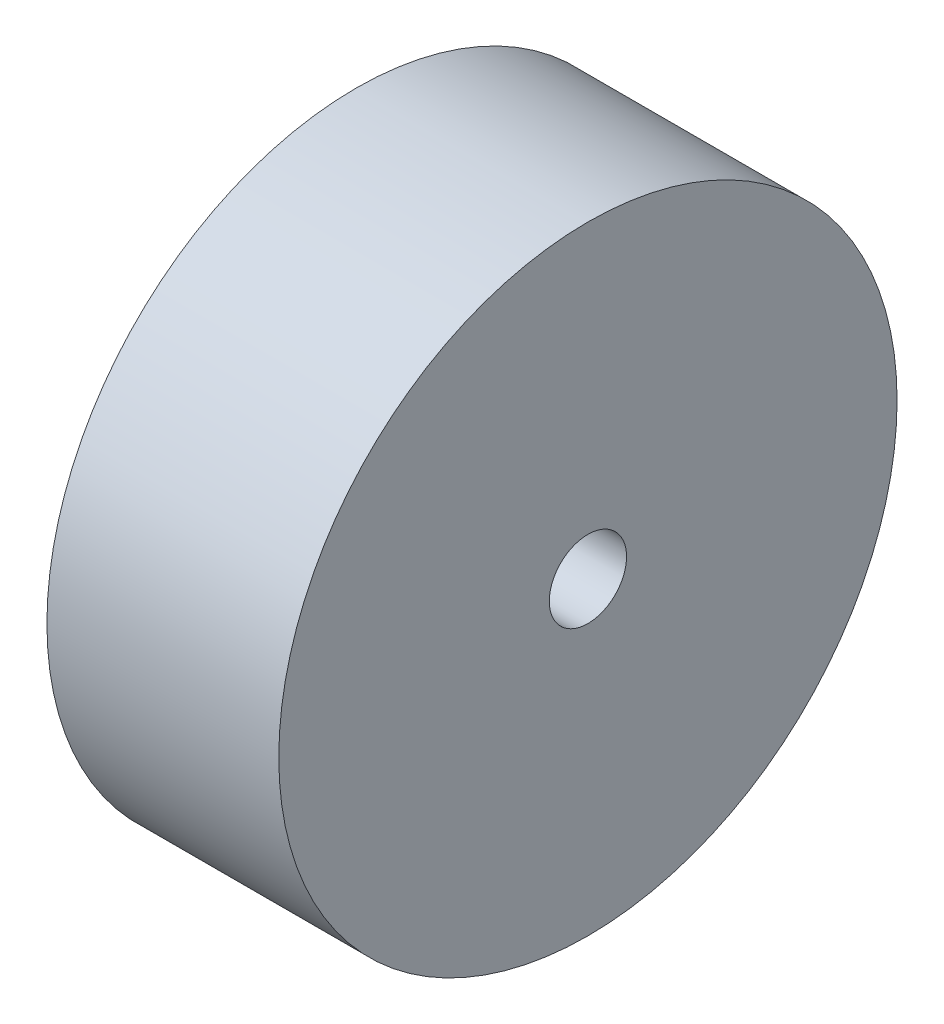
SolidWorks part; units mm, degrees
ref_plane "Front Plane" through (0, 0, 0) normal (0, 0, 1) x (1, 0, 0)
ref_plane "Top Plane" through (0, 0, 0) normal (0, 1, 0) x (1, 0, 0)
ref_plane "Right Plane" through (0, 0, 0) normal (1, 0, 0) x (0, 0, -1)
sketch "Sketch1" plane through (0, 0, 0) normal (1, 0, 0) x (0, 0, -1)
  circle A0 centre (0, 0) radius 101.6
  circle A1 centre (0, 0) radius 12.7
  dimension "D1" = 203.2
  dimension "D2" = 25.4
extrude "Boss-Extrude1" add sketch "Sketch1" along normal blind 76.2
ref_axis "Axis1" through (75.1904, 0, 0) along (-1, 0, 0)
